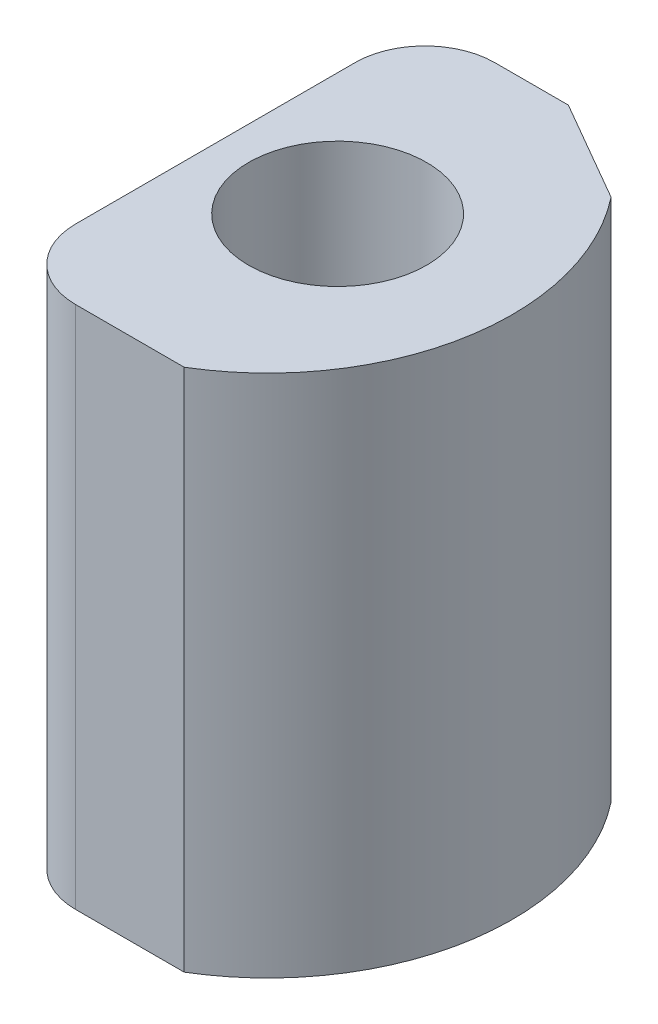
SolidWorks part; units mm, degrees
material "Rubber"
ref_plane "Front Plane" through (0, 0, 0) normal (0, 0, 1) x (1, 0, 0)
ref_plane "Top Plane" through (0, 0, 0) normal (0, 1, 0) x (1, 0, 0)
ref_plane "Right Plane" through (0, 0, 0) normal (1, 0, 0) x (0, 0, -1)
sketch "Sketch1" plane through (0, 0, 0) normal (0, 1, 0) x (1, 0, 0)
  line L0 (3.2111, 12) -> (-7, 12)
  line L1 (-7, 12) -> (-7, -12)
  line L2 (-7, -12) -> (3.2111, -12)
  circle A0 centre (0, 0) radius 5.1
  arc A1 (3.2111, 12) -> (3.2111, -12) centre (-4, 0) cw
  dimension "D1" = 10.2
  dimension "D6" = 14
  dimension "D2" = 12
  dimension "D3" = 12
  dimension "D4" = 7
  dimension "D5" = 4
  dimension "D7" = 12
extrude "Boss-Extrude1" add sketch "Sketch1" along normal blind 30
fillet "Fillet1" radius 4 2 edges at (-7, 15, -12) (-7, 15, 12)
chamfer "Chamfer1" distance 2 angle 30 1 edges at (3.2111, 15, -12) first distance on face at (0.1056, 15, -12)
